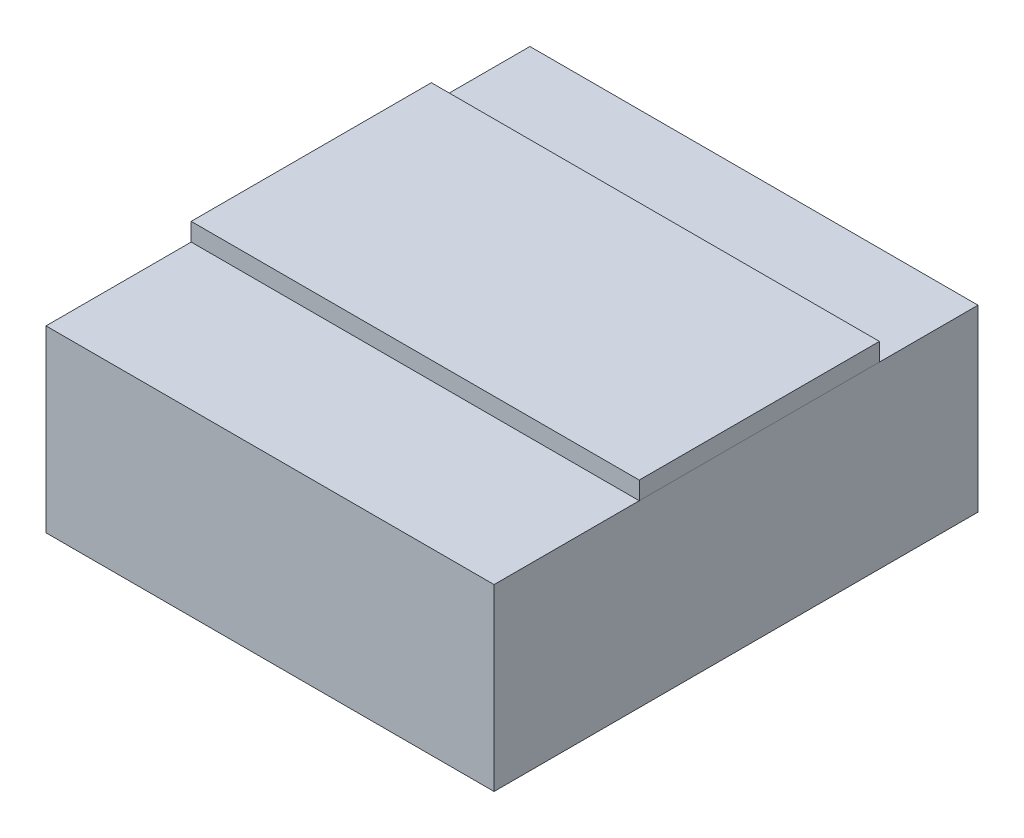
SolidWorks part; units mm, degrees
ref_plane "Front Plane" through (0, 0, 0) normal (0, 0, 1) x (1, 0, 0)
ref_plane "Top Plane" through (0, 0, 0) normal (0, 1, 0) x (1, 0, 0)
ref_plane "Right Plane" through (0, 0, 0) normal (1, 0, 0) x (0, 0, -1)
sketch "Sketch1" plane through (0, 0, 0) normal (0, 1, 0) x (1, 0, 0)
  line L1 (52.1591, -14.8846) -> (77.1591, -14.8846)
  line L2 (52.1591, -14.8846) -> (52.1591, -41.8846)
  line L3 (52.1591, -41.8846) -> (77.1591, -41.8846)
  line L4 (77.1591, -14.8846) -> (77.1591, -41.8846)
  line L5 (52.1591, -14.8846) -> (77.1591, -41.8846) construction
  line L6 (52.1591, -41.8846) -> (77.1591, -14.8846) construction
  point P0 (64.6591, -28.3846)
  dimension "D1" = 27
  dimension "D2" = 25
extrude "Boss-Extrude1" add sketch "Sketch1" along normal blind 10
sketch "Sketch2" plane through (0, 10, 0) normal (0, 1, 0) x (1, 0, 0)
  line L0 (77.1591, -41.8846) -> (77.1591, -14.8846) construction
  line L1 (52.1591, -33.7846) -> (77.1591, -33.7846)
  line L2 (52.1591, -33.7846) -> (52.1591, -20.3846)
  line L3 (52.1591, -20.3846) -> (77.1591, -20.3846)
  line L4 (77.1591, -33.7846) -> (77.1591, -20.3846)
  line L5 (52.1591, -33.7846) -> (77.1591, -20.3846) construction
  line L6 (52.1591, -20.3846) -> (77.1591, -33.7846) construction
  line L7 (52.1591, -14.8846) -> (52.1591, -41.8846) construction
  line L8 (77.1591, -14.8846) -> (52.1591, -14.8846) construction
  point P0 (64.6591, -27.0846)
  dimension "D1" = 13.4
  dimension "D2" = 5.5
extrude "Boss-Extrude2" add sketch "Sketch2" along normal blind 1 separate body
